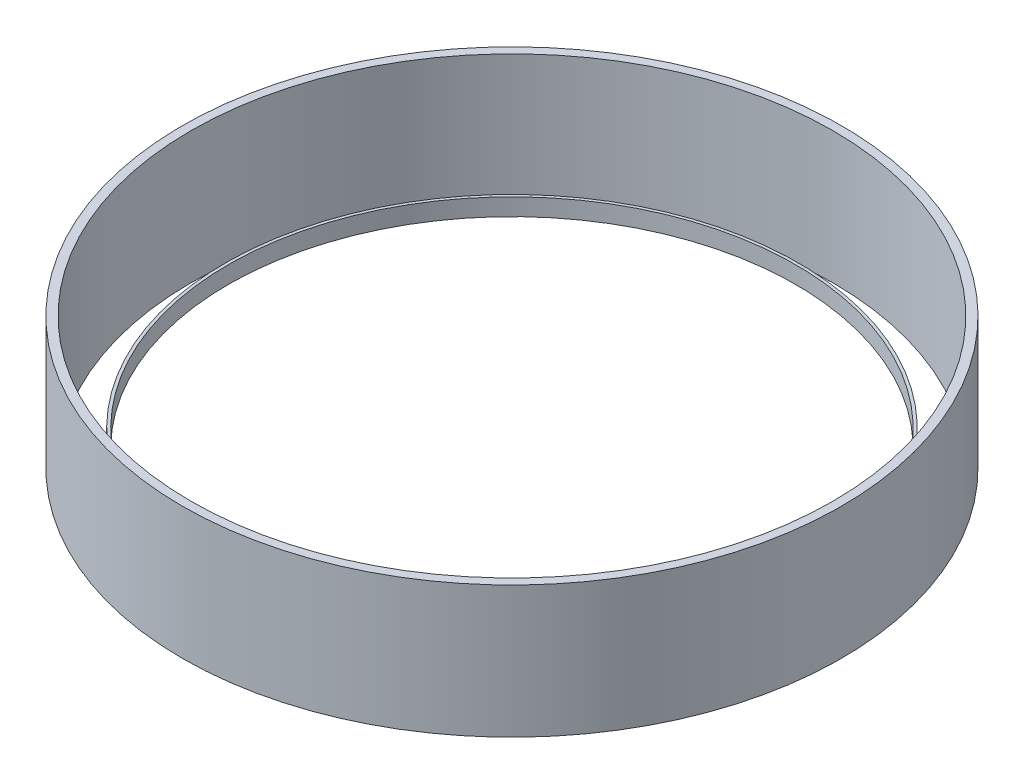
SolidWorks part; units mm, degrees
ref_plane "Front Plane" through (0, 0, 0) normal (0, 0, 1) x (1, 0, 0)
ref_plane "Top Plane" through (0, 0, 0) normal (0, 1, 0) x (1, 0, 0)
ref_plane "Right Plane" through (0, 0, 0) normal (1, 0, 0) x (0, 0, -1)
ref_axis "Axis1" through (0, 26.875, 0) along (0, -1, 0)
ref_plane "Plane1" through (0, 0, 0) normal (0.3827, 0, 0.9239) x (0.9239, 0, -0.3827)
ref_plane "Plane2" through (0, 0, 0) normal (0.3827, 0, -0.9239) x (-0.9239, 0, -0.3827)
sketch "Sketch27" plane through (0, 0, 0) normal (0, 1, 0) x (1, 0, 0)
  circle A0 centre (0, 0) radius 50
  circle A1 centre (0, 0) radius 49.5
  dimension "D1" = 100
  dimension "D2" = 99
extrude "Boss-Extrude10" add sketch "Sketch27" along normal blind 3
sketch "Sketch28" plane through (0, 0, 0) normal (0, 1, 0) x (1, 0, 0)
  circle A0 centre (0, 0) radius 56
  circle A1 centre (0, 0) radius 57.5
  dimension "D1" = 112
  dimension "D2" = 115
extrude "Boss-Extrude11" add sketch "Sketch28" along normal blind 20 and the other way blind 3 separate body
